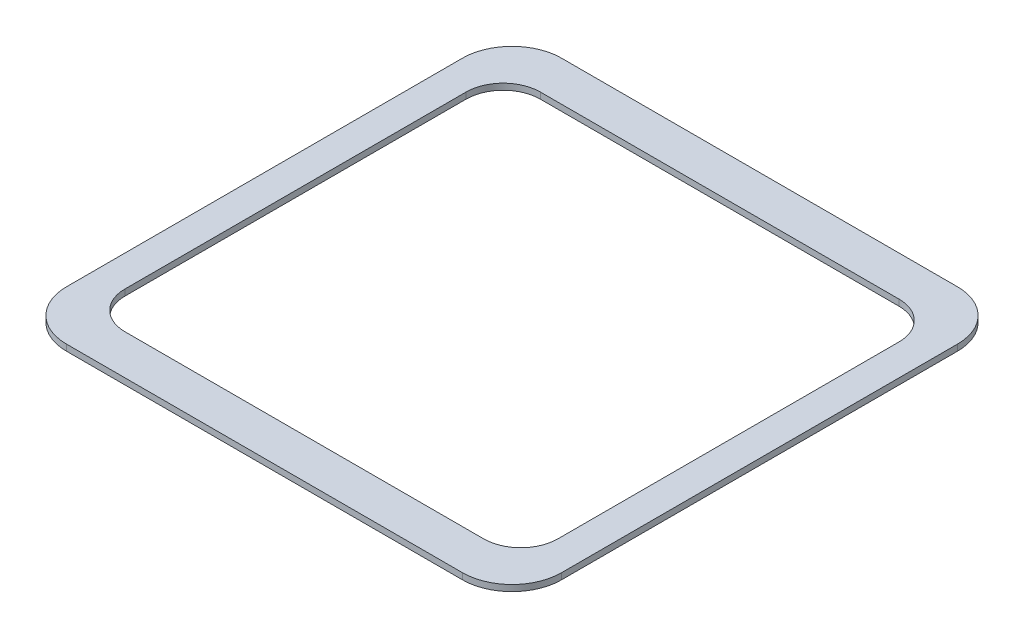
SolidWorks part; units mm, degrees
ref_plane "Front Plane" through (0, 0, 0) normal (0, 0, 1) x (1, 0, 0)
ref_plane "Top Plane" through (0, 0, 0) normal (0, 1, 0) x (1, 0, 0)
ref_plane "Right Plane" through (0, 0, 0) normal (1, 0, 0) x (0, 0, -1)
sketch "Sketch2" plane through (0, 49.0346, 0) normal (0, 1, 0) x (1, 0, 0)
  line L23 (36.6125, 86.6466) -> (-64.9875, 86.6466)
  line L24 (49.3125, -27.6534) -> (49.3125, 73.9466)
  line L26 (-60.1797, -30.1159) -> (31.8047, -30.1159)
  line L32 (-64.9875, -40.3534) -> (36.6125, -40.3534) construction
  line L33 (-77.6875, 73.9466) -> (-77.6875, -27.6534) construction
  line L34 (-64.9875, -40.3534) -> (36.6125, -40.3534)
  line L35 (-77.6875, 73.9466) -> (-77.6875, -27.6534)
  line L40 (41.3284, -20.5922) -> (41.3284, 66.8854)
  line L42 (-69.7035, 66.8854) -> (-69.7035, 23.1466)
  line L43 (-69.7035, 23.1466) -> (-69.7035, -20.5922)
  line L45 (41.3284, -20.5922) -> (41.3284, 66.8854)
  line L47 (-69.7035, 66.8854) -> (-69.7035, 23.1466)
  line L48 (-69.7035, 23.1466) -> (-69.7035, -20.5922)
  line L64 (-60.1797, -30.1159) -> (31.8047, -30.1159)
  line L66 (31.8047, 76.4092) -> (-60.1797, 76.4092)
  line L67 (31.8047, 76.4092) -> (-60.1797, 76.4092)
  arc A2 (49.3125, 73.9466) -> (36.6125, 86.6466) centre (36.6125, 73.9466) ccw
  arc A17 (-64.9875, 86.6466) -> (-77.6875, 73.9466) centre (-64.9875, 73.9466) ccw
  arc A21 (-69.7035, -20.5922) -> (-60.1797, -30.1159) centre (-60.1797, -20.5922) ccw
  arc A22 (-69.7035, -20.5922) -> (-60.1797, -30.1159) centre (-60.1797, -20.5922) ccw
  arc A23 (31.8047, -30.1159) -> (41.3284, -20.5922) centre (31.8047, -20.5922) ccw
  arc A24 (31.8047, -30.1159) -> (41.3284, -20.5922) centre (31.8047, -20.5922) ccw
  arc A25 (41.3284, 66.8854) -> (31.8047, 76.4092) centre (31.8047, 66.8854) ccw
  arc A26 (41.3284, 66.8854) -> (31.8047, 76.4092) centre (31.8047, 66.8854) ccw
  arc A27 (-60.1797, 76.4092) -> (-69.7035, 66.8854) centre (-60.1797, 66.8854) ccw
  arc A28 (-60.1797, 76.4092) -> (-69.7035, 66.8854) centre (-60.1797, 66.8854) ccw
  arc A29 (36.6125, -40.3534) -> (49.3125, -27.6534) centre (36.6125, -27.6534) ccw construction
  arc A30 (-77.6875, -27.6534) -> (-64.9875, -40.3534) centre (-64.9875, -27.6534) ccw construction
  arc A31 (36.6125, -40.3534) -> (49.3125, -27.6534) centre (36.6125, -27.6534) ccw
  arc A32 (-77.6875, -27.6534) -> (-64.9875, -40.3534) centre (-64.9875, -27.6534) ccw
  dimension "D1" = 1.5875
extrude "MainBody" add sketch "Sketch2" along normal blind 1.5875
equation "\"ClampDepth\"= 3 / 8in"
equation "\"D1@Sketch2\"=0.0625"
